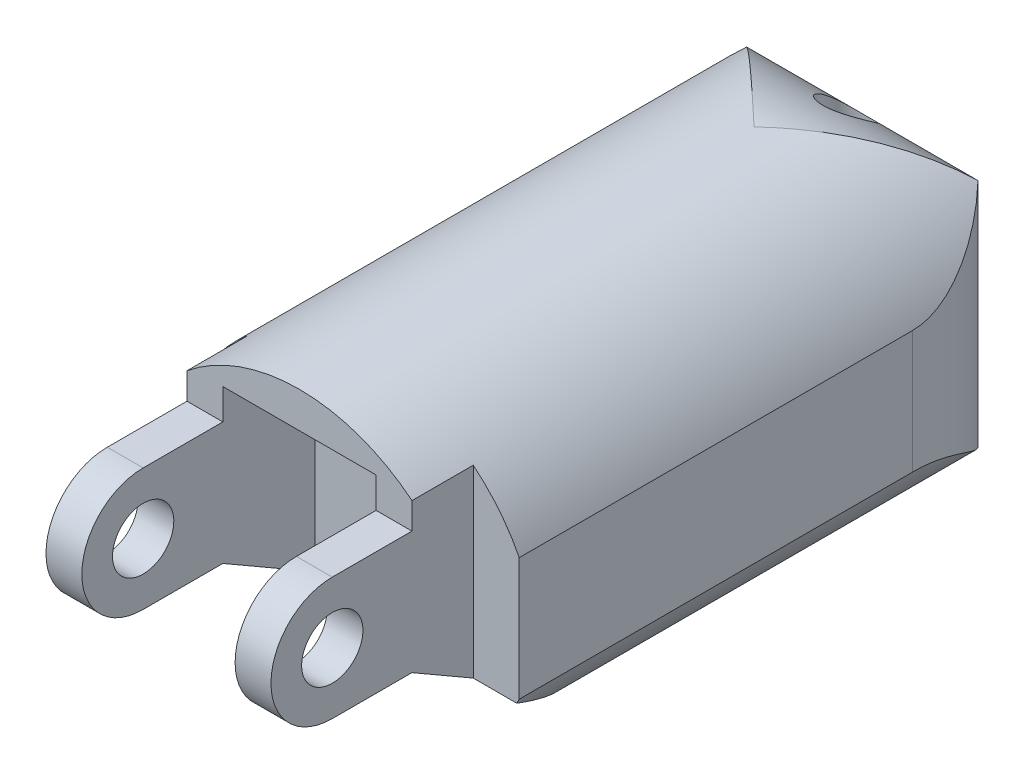
SolidWorks part; units mm, degrees
material "PET"
ref_plane "Front Plane" through (0, 0, 0) normal (0, 0, 1) x (1, 0, 0)
ref_plane "Top Plane" through (0, 0, 0) normal (0, 1, 0) x (1, 0, 0)
ref_plane "Right Plane" through (0, 0, 0) normal (1, 0, 0) x (0, 0, -1)
sketch "Sketch1" plane through (0, 0, 0) normal (0, 0, 1) x (1, 0, 0)
  line L0 (0, 0) -> (0, 5.08)
  line L3 (13.1318, 5.08) -> (13.1318, 0)
  arc A2 (0, 5.08) -> (13.1318, 5.08) centre (6.5659, 1.7387) cw
  arc A3 (0, 0) -> (13.1318, 0) centre (6.5659, 3.3413) ccw
  point P7 (6.5659, -4.0259)
  point P8 (6.5659, 9.1059)
  dimension "D1" = 13.1318
  dimension "D2" = 13.1318
  dimension "D3" = 5.08
extrude "Boss-Extrude1" add sketch "Sketch1" along normal mid plane 25.4 contours A2 L3 A3 L0
sketch "Sketch2" plane through (0, 0, 0) normal (1, 0, 0) x (0, 0, -1)
  line L4 (15.875, 2.54) -> (-49984.125, 2.54) construction
  line L5 (12.7, 5.08) -> (12.7, 0) construction
  line L6 (-12.7, 5.08) -> (-12.7, 0) construction
  line L7 (-12.7, -4.0259) -> (-12.7, 1.27)
  line L8 (-3.5272, -4.0259) -> (-12.7, -4.0259)
  line L9 (-12.7, 1.27) -> (-3.5272, -4.0259)
  line L10 (0, -1000) -> (0, 49000) construction
  line L30 (-12.7, 0) -> (-12.7, -4.0259) construction
  point P0 (-15.0884, 2.54)
  point P11 (12.7, 2.54)
  point P14 (-12.7, 2.54)
  dimension "D1" = 60
  dimension "D2" = 1.27
extrude "Cut-Extrude1" cut sketch "Sketch2" along normal through all
sketch "Sketch3" plane through (0, 0, 12.7) normal (0, 0, 1) x (1, 0, 0)
  line L3 (-4.9679, 2.54) -> (22.8791, 2.54) construction
  line L6 (0, 0) -> (0, 5.08) construction
  line L9 (6.5659, -996.7054) -> (6.5659, 49003.2946) construction
  arc A8 (3.5004, -1.9292) -> (9.6314, -1.9292) centre (6.5659, -2.7559) cw
  arc A13 (1.1319, 0.576) -> (11.9999, 0.576) centre (6.5659, 3.3413) ccw
  arc A14 (1.1319, 0.576) -> (11.9999, 0.576) centre (6.5659, 3.3413) ccw
  point P4 (0, 2.54)
  dimension "D1" = 1.27
  dimension "D2" = 3.175
extrude "Cut-Extrude2" cut sketch "Sketch3" against normal through all contours A8 region at (6.5659, -1.2709, 12.7)
ref_plane "Plane1" through (0, 0, 0) normal (0, 0, -1) x (-1, 0, 0)
ref_point "Point1"
ref_plane "Plane2" through (6.5659, 0, 0) normal (1, 0, 0) x (0, 0, -1)
sketch "Sketch4" plane through (0, 0, 0) normal (-1, 0, 0) x (0, 0, 1)
  line L0 (-12.7, -4.0259) -> (3.5272, -4.0259) construction
  line L1 (-12.7, 0) -> (-12.7, -4.0259) construction
  line L2 (-12.7, 5.08) -> (-12.7, 0) construction
  line L3 (-12.7, 9.1059) -> (-12.7, 5.08) construction
  line L4 (12.7, 9.1059) -> (-12.7, 9.1059) construction
  line L5 (-12.7, -4.0259) -> (3.5272, -4.0259)
  line L6 (-12.7, 0) -> (-12.7, -4.0259)
  line L7 (-12.7, 5.08) -> (-12.7, 0)
  line L8 (-12.7, 9.1059) -> (-12.7, 5.08)
  line L9 (12.7, 9.1059) -> (-12.7, 9.1059)
  arc A0 (-6.1341, 9.1059) -> (-6.1341, -4.0259) centre (-6.1341, 2.54) ccw
  point P9 (-12.7, 2.54)
  point P10 (-12.7, 2.54)
  line M1 (-12.7, 0) -> (10.5003, 0)
  line M3 (12.7, 5.08) -> (-12.7, 5.08)
  line M4 (-12.7, 5.08) -> (-12.7, 0)
extrude "Cut-Extrude3" cut sketch "Sketch4" against normal through all contours A0 L9 L8 M3 | A0 M3 M4 | A0 L7 M1 | A0 L6 L5 M1 region at (0, -2.7132, -11.17) region at (0, 4.45, -12.5477) region at (0, 0.63, -12.5477) region at (0, 7.7932, -11.17)
sketch "Sketch5" plane through (0, 0, 0) normal (0, 1, 0) x (1, 0, 0)
  line L0 (13.1318, 12.7) -> (0, 12.7) construction
  line L1 (13.1318, 12.1888) -> (13.1318, 12.7) construction
  line L2 (13.1318, -12.7) -> (13.1318, 12.1888) construction
  line L3 (0, -12.7) -> (0, 12.1888) construction
  line L4 (13.1318, 12.7) -> (0, 12.7)
  line L5 (13.1318, 12.1888) -> (13.1318, 12.7)
  line L6 (13.1318, -12.7) -> (13.1318, 12.1888)
  line L7 (0, -12.7) -> (0, 12.1888)
  line L8 (0, 12.1888) -> (0, 12.7)
  arc A0 (0, 6.1341) -> (13.1318, 6.1341) centre (6.5659, 6.1341) cw
  point P9 (6.5659, 12.7)
  point P10 (6.5659, 12.7)
extrude "Cut-Extrude4" cut sketch "Sketch5" against normal through all both and the other way through all contours L4 A0 L6 L5 | L7 A0 L4 L8 region at (11.6652, 0, -11.2334) region at (1.4666, 0, -11.2334)
ref_plane "Plane3" through (2.54, 0, 0) normal (1, 0, 0) x (0, 0, -1)
ref_plane "Plane4" through (10.5918, 0, 0) normal (1, 0, 0) x (0, 0, -1)
sketch "Sketch8" plane through (2.54, 0, 0) normal (1, 0, 0) x (0, 0, -1)
  line L0 (-12.7, 6.35) -> (-16.002, 6.35)
  line L1 (-12.7, 5.08) -> (-12.7, 1.27) construction
  line L2 (-12.7, 6.35) -> (-12.7, 1.27)
  line L3 (-12.7, 1.27) -> (-16.002, 1.27)
  line L4 (-12.7, 5.08) -> (-12.7, 0) construction
  line L5 (-10.5003, 0) -> (6.1341, 0) construction
  line L6 (-12.7, 1.27) -> (-12.7, 0) construction
  line L7 (-12.7, 0) -> (-16.1427, 0) construction
  arc A0 (-16.002, 6.35) -> (-16.002, 1.27) centre (-16.002, 3.81) ccw
  circle A1 centre (-16.002, 3.81) radius 1.27
  dimension "D1" = 2.54
  dimension "D2" = 5.08
  dimension "D3" = 3.302
  dimension "D4" = 3.81
extrude "Boss-Extrude3" add sketch "Sketch8" along normal mid plane 1.27
ref_plane "Plane5" through (6.5659, 0, 0) normal (1, 0, 0) x (0, 0, -1)
sketch "Sketch10" plane through (1.905, 0, 0) normal (-1, 0, 0) x (0, 0, 1)
  line L3 (12.7, 6.35) -> (12.7, 1.27)
  line L4 (12.7, 1.27) -> (16.002, 1.27)
  line L5 (16.002, 6.35) -> (12.7, 6.35)
  line L6 (12.7, 6.35) -> (12.7, 1.27)
  line L7 (12.7, 1.27) -> (16.002, 1.27)
  line L8 (16.002, 6.35) -> (12.7, 6.35)
  circle A0 centre (16.002, 3.81) radius 1.27 construction
  arc A1 (16.002, 1.27) -> (16.002, 6.35) centre (16.002, 3.81) ccw
  arc A2 (16.002, 1.27) -> (16.002, 6.35) centre (16.002, 3.81) ccw
  circle A3 centre (16.002, 3.81) radius 1.27
  dimension "D1" = 0
extrude "Boss-Extrude4" add sketch "Sketch10" along normal blind 1.27
mirror "Mirror1" about plane through (6.5659, 0, 0) normal (1, 0, 0) of "Boss-Extrude4", "Boss-Extrude3"
sketch "Sketch11" plane through (0.635, 0, 0) normal (-1, 0, 0) x (0, 0, 1)
  line L3 (16.002, 6.35) -> (12.7, 6.35)
  line L4 (12.7, 6.109) -> (12.7, 1.27)
  line L5 (12.7, 1.27) -> (16.002, 1.27)
  line L6 (16.002, 6.35) -> (12.7, 6.35)
  line L7 (12.7, 6.109) -> (12.7, 1.27)
  line L8 (12.7, 1.27) -> (16.002, 1.27)
  line L10 (12.7, 6.35) -> (12.7, 6.109)
  line L11 (12.7, 6.35) -> (12.7, 6.109)
  circle A0 centre (16.002, 3.81) radius 1.27 construction
  circle A1 centre (16.002, 3.81) radius 1.27
  arc A3 (16.002, 1.27) -> (16.002, 6.35) centre (16.002, 3.81) ccw
  arc A4 (16.002, 1.27) -> (16.002, 6.35) centre (16.002, 3.81) ccw
  dimension "D1" = 0
extrude "Cut-Extrude6" cut sketch "Sketch11" against normal blind 1.27
sketch "Sketch12" plane through (3.175, 0, 0) normal (1, 0, 0) x (0, 0, -1)
  line L3 (-12.7, 1.27) -> (-12.7, 6.35)
  line L4 (-12.7, 6.35) -> (-16.002, 6.35)
  line L5 (-16.002, 1.27) -> (-12.7, 1.27)
  line L6 (-12.7, 1.27) -> (-12.7, 6.35)
  line L7 (-12.7, 6.35) -> (-16.002, 6.35)
  line L8 (-16.002, 1.27) -> (-12.7, 1.27)
  circle A0 centre (-16.002, 3.81) radius 1.27 construction
  arc A1 (-16.002, 6.35) -> (-16.002, 1.27) centre (-16.002, 3.81) ccw
  arc A2 (-16.002, 6.35) -> (-16.002, 1.27) centre (-16.002, 3.81) ccw
  circle A3 centre (-16.002, 3.81) radius 1.27
  dimension "D1" = 0
extrude "Boss-Extrude5" add sketch "Sketch12" along normal blind 1.27
mirror "Mirror2" about plane through (6.5659, 0, 0) normal (1, 0, 0) of "Cut-Extrude6", "Boss-Extrude5"
sketch "Sketch13" plane through (0, 0, 12.7) normal (0, 0, 1) x (1, 0, 0)
  line L1 (0, -4.0259) -> (1.905, -4.0259)
  line L2 (0, -4.0259) -> (0, 7.4441)
  line L3 (0, 7.4441) -> (1.905, 7.4441)
  line L4 (1.905, -4.0259) -> (1.905, 7.4441)
  line L5 (6.5659, 0.762) -> (6.5659, 14.3113) construction
  line L6 (1.905, 6.35) -> (1.905, 1.27) construction
  line L7 (11.2268, -4.0259) -> (11.2268, 7.4441)
  line L8 (13.1318, 7.4441) -> (11.2268, 7.4441)
  line L9 (13.1318, -4.0259) -> (13.1318, 7.4441)
  line L10 (13.1318, -4.0259) -> (11.2268, -4.0259)
  line L11 (3.2723, -4.0259) -> (13.6472, -4.0259) construction
  line L12 (0, 1.27) -> (0, 5.08) construction
  line L14 (4.445, 0.762) -> (8.6868, 0.762) construction
  line L15 (8.6868, 1.27) -> (8.6868, 6.35) construction
  line L17 (4.445, 1.27) -> (4.445, 6.35) construction
  arc A0 (0, 0) -> (13.1318, 0) centre (6.5659, 3.3413) ccw construction
  arc A1 (13.1318, 5.08) -> (0, 5.08) centre (6.5659, 1.7387) ccw construction
extrude "Cut-Extrude7" cut sketch "Sketch13" against normal blind 2.54
sketch "Sketch14" plane through (0, 0, 12.7) normal (0, 0, 1) x (1, 0, 0)
  line L0 (4.445, -1.27) -> (8.6868, -1.27)
  line L5 (4.445, 1.27) -> (4.445, 6.35) construction
  line L6 (8.6868, 1.27) -> (8.6868, 6.35) construction
  line L9 (4.445, -1.27) -> (4.445, 7.62)
  line L10 (4.445, 7.62) -> (8.6868, 7.62)
  line L11 (8.6868, 7.62) -> (8.6868, -1.27)
  line M13 (4.445, 1.27) -> (8.6868, 1.27)
  dimension "D3" = 8.89
  dimension "D4" = 1.27
extrude "Cut-Extrude8" cut sketch "Sketch14" against normal blind 3.81 contours M13 | L11 L0 L9 L10 region at (6.5659, 0, 12.7)
sketch "Sketch18" plane through (0, 0, 0) normal (0, 1, 0) x (1, 0, 0)
  circle A1 centre (6.5659, 9.9441) radius 0.9525
  arc A2 (11.3592, 10.6213) -> (6.5659, 12.7) centre (6.5659, 6.1341) ccw construction
  dimension "D1" = 1.905
  dimension "D2" = 3.81
extrude "Cut-Extrude12" cut sketch "Sketch18" along normal up to surface (8.4515 mm away) up to face at (6.5659, 6.8173, -10.5424)
ref_plane "Plane6" through (6.5659, 0, 0) normal (-1, 0, 0) x (0, 0, 1)
sketch "Sketch19" plane through (6.5659, 0, 0) normal (-1, 0, 0) x (0, 0, 1)
  line L18 (12.7, 6.35) -> (12.7, 7.62)
  line L19 (12.7, 1.27) -> (16.002, 1.27)
  line L20 (16.002, 6.35) -> (12.7, 6.35)
  line L24 (12.7, 6.35) -> (12.7, 7.62)
  line L25 (12.7, 7.62) -> (8.89, 7.62)
  line L26 (12.7, 1.27) -> (16.002, 1.27)
  line L27 (16.002, 6.35) -> (12.7, 6.35)
  line L31 (8.89, -0.3932) -> (9.8193, -0.3932)
  line L32 (12.7, 7.62) -> (8.89, 7.62)
  line L33 (8.89, 7.62) -> (8.89, -0.3932)
  line L34 (8.89, 7.62) -> (8.89, -0.3932)
  line L35 (8.89, -0.3932) -> (9.8193, -0.3932)
  line L36 (9.8193, -0.3932) -> (12.7, 1.27)
  line L37 (9.8193, -0.3932) -> (12.7, 1.27)
  circle A1 centre (16.002, 3.81) radius 1.27
  circle A2 centre (16.002, 3.81) radius 1.27
  arc A5 (16.002, 1.27) -> (16.002, 6.35) centre (16.002, 3.81) ccw
  arc A6 (16.002, 1.27) -> (16.002, 6.35) centre (16.002, 3.81) ccw
  dimension "D1" = 0
  dimension "D2" = 0
extrude "Cut-Extrude13" cut sketch "Sketch19" against normal mid plane 6.35
sketch "Sketch20" plane through (6.5659, 0, 0) normal (-1, 0, 0) x (0, 0, 1)
  line L1 (8.89, 4.9293) -> (13.2657, 4.9293)
  line L3 (8.89, -1.926) -> (13.2657, -1.926)
  line L4 (13.2657, 4.9293) -> (13.2657, -1.926)
  line L5 (8.89, -1.926) -> (8.89, 4.9293)
  line L7 (8.89, -0.3932) -> (8.89, 0.4191) construction
  line L8 (8.89, -0.3932) -> (8.89, 0.4191)
  point P6 (8.89, 0.013)
extrude "Cut-Extrude14" cut sketch "Sketch20" against normal mid plane 6.35 contours L5 L3 L4 L1 region at (6.5659, 1.5016, 11.0779)
sketch "Sketch21" plane through (0, 0, 8.89) normal (0, 0, 1) x (1, 0, 0)
  line L0 (9.7409, 3.81) -> (11.2268, 3.81) construction
  line L1 (3.8989, -0.2286) -> (9.2329, -0.2286)
  line L2 (3.8989, -0.2286) -> (3.8989, 5.461)
  line L3 (3.8989, 5.461) -> (9.2329, 5.461)
  line L4 (9.2329, -0.2286) -> (9.2329, 5.461)
  line L5 (3.8989, -0.2286) -> (9.2329, 5.461) construction
  line L6 (3.8989, 5.461) -> (9.2329, -0.2286) construction
  line L7 (8.5979, 5.08) -> (9.2329, 5.08) construction
  line L8 (8.5979, 5.461) -> (9.2329, 5.461)
  line L9 (8.5979, 4.699) -> (9.2329, 4.699)
  arc A0 (9.1631, -0.9297) -> (3.9687, -0.9297) centre (6.5659, -2.7559) ccw construction
  arc A1 (8.5979, 5.461) -> (8.5979, 4.699) centre (8.5979, 5.08) ccw
  arc A2 (9.2329, 4.699) -> (9.2329, 5.461) centre (9.2329, 5.08) ccw
  point P0 (6.5659, 2.6162)
  point P8 (6.5659, 0.4191)
  point P13 (8.9154, 5.08)
  dimension "D1" = 1.651
  dimension "D2" = 5.6896
  dimension "D3" = 5.334
  dimension "D4" = 0.635
  dimension "D5" = 0.762
extrude "Cut-Extrude15" cut sketch "Sketch21" against normal blind 17.78 contours L3 A1 L9 L4 | A2 L8 A1 L9 region at (8.7619, 5.08, 8.89)
sketch "Sketch22" plane through (0, 0, 0) normal (-1, 0, 0) x (0, 0, 1)
  text T0 "Pinky 1\r\n"
extrude "Cut-Extrude16" cut sketch "Sketch22" against normal blind 1
fillet "Fillet1" radius 1.27 1 edges at (6.7383, 0.4144, -9.0073)
equation "\"D2@Sketch1\"   = 0.517"
equation "\"D1@Boss-Extrude1\"=1"
